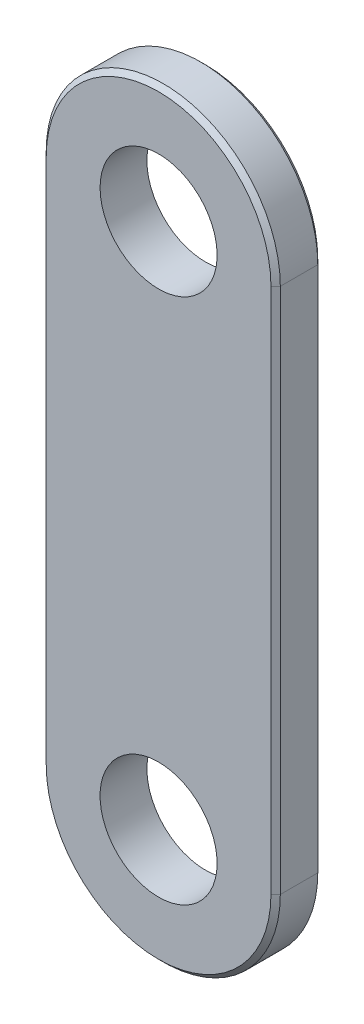
SolidWorks part; units mm, degrees
ref_plane "Front Plane" through (0, 0, 0) normal (0, 0, 1) x (1, 0, 0)
ref_plane "Top Plane" through (0, 0, 0) normal (0, 1, 0) x (1, 0, 0)
ref_plane "Right Plane" through (0, 0, 0) normal (1, 0, 0) x (0, 0, -1)
sketch "Sketch1" plane through (0, 0, 0) normal (0, 0, 1) x (1, 0, 0)
  line L0 (-50, 0) -> (-50, 225)
  line L1 (50, 0) -> (50, 225)
  circle A0 centre (0, 0) radius 25
  arc A1 (-50, 0) -> (50, 0) centre (0, 0) ccw
  circle A2 centre (0, 225) radius 25
  arc A3 (-50, 225) -> (50, 225) centre (0, 225) cw
  point P7 (0, 0)
  dimension "D1" = 50
  dimension "D2" = 225
  dimension "D3" = 50
  dimension "D4" = 100
extrude "Boss-Extrude1" add sketch "Sketch1" along normal blind 10 and the other way blind 10
chamfer "Chamfer1" distance 2 angle 45 8 edges at (-50, 112.5, -10) (0, -50, -10) (0, 275, -10) (50, 112.5, -10) (0, -50, 10) (50, 112.5, 10) (-50, 112.5, 10) (0, 275, 10)
